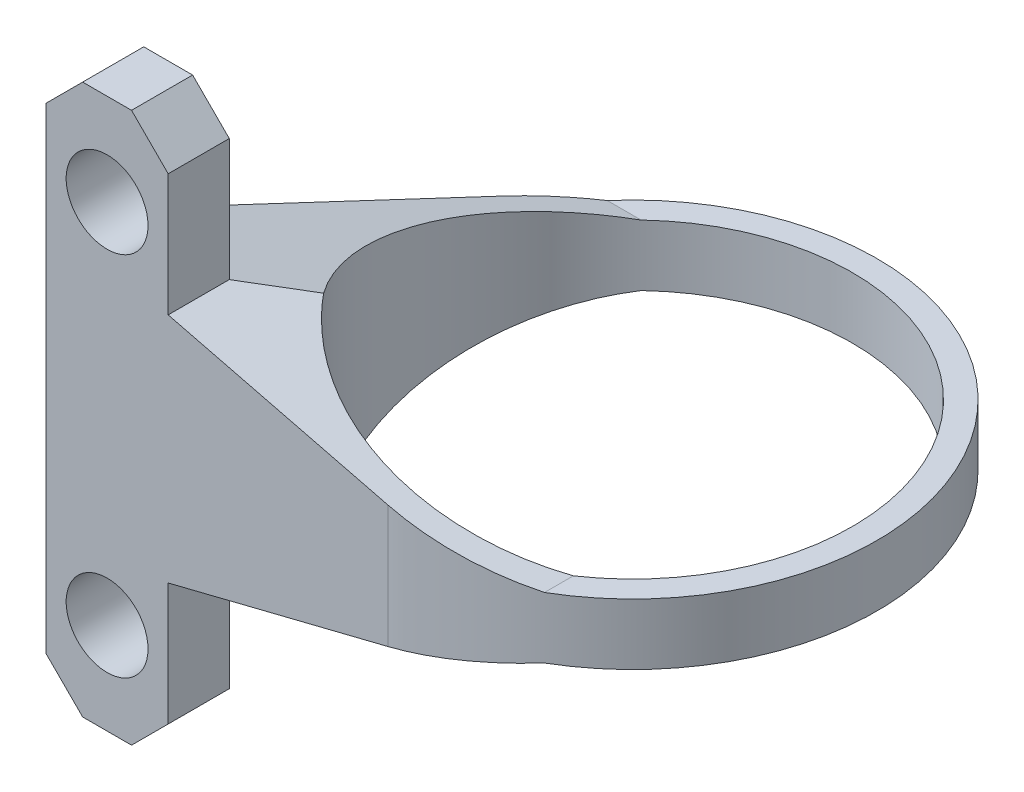
SolidWorks part; units mm, degrees
ref_plane "Front Plane" through (0, 0, 0) normal (0, 0, 1) x (1, 0, 0)
ref_plane "Top Plane" through (0, 0, 0) normal (0, 1, 0) x (1, 0, 0)
ref_plane "Right Plane" through (0, 0, 0) normal (1, 0, 0) x (0, 0, -1)
sketch "Sketch1" plane through (0, 0, 0) normal (0, 0, 1) x (1, 0, 0)
  line L0 (0, 15) -> (0, -15) construction
  line L1 (-5, 22.5) -> (5, 22.5)
  line L2 (-5, 22.5) -> (-5, -22.5)
  line L3 (-5, -22.5) -> (5, -22.5)
  line L4 (5, 22.5) -> (5, -22.5)
  line L5 (-5, 22.5) -> (5, -22.5) construction
  line L6 (-5, -22.5) -> (5, 22.5) construction
  circle A0 centre (0, 15) radius 3.35
  circle A1 centre (0, -15) radius 3.35
  point P0 (0, 0)
  dimension "D4" = 6.7
  dimension "D1" = 10
  dimension "D2" = 45
  dimension "D3" = 30
extrude "Boss-Extrude1" add sketch "Sketch1" along normal blind 5
sketch "Sketch2" plane through (0, 0, 0) normal (0, 1, 0) x (1, 0, 0)
  line L0 (5, -5) -> (5, 0) construction
  line L3 (5, -3) -> (23, -3) construction
  line L4 (23, -5) -> (5, -5)
  line L5 (5, -5) -> (5, 0)
  line L6 (5, 0) -> (-5, 0)
  line L7 (-5, 0) -> (4.5626, 22.7499)
  circle A0 centre (23, 15) radius 18
  arc A2 (23, -5) -> (4.5626, 22.7499) centre (23, 15) ccw
  circle A3 centre (23, 15) radius 20 construction
  dimension "D1" = 36
  dimension "D2" = 2
extrude "Boss-Extrude2" add sketch "Sketch2" along normal blind 2.5 and the other way blind 2.5
chamfer "Chamfer1" distance 3 angle 45 4 edges at (-5, -22.5, 2.5) (5, -22.5, 2.5) (5, 22.5, 2.5) (-5, 22.5, 2.5)
chamfer "Chamfer2" distance 7 angle 76 4 edges at (5, 2.5, 2.5) (0, 2.5, 0) (5, -2.5, 2.5) (0, -2.5, 0)
